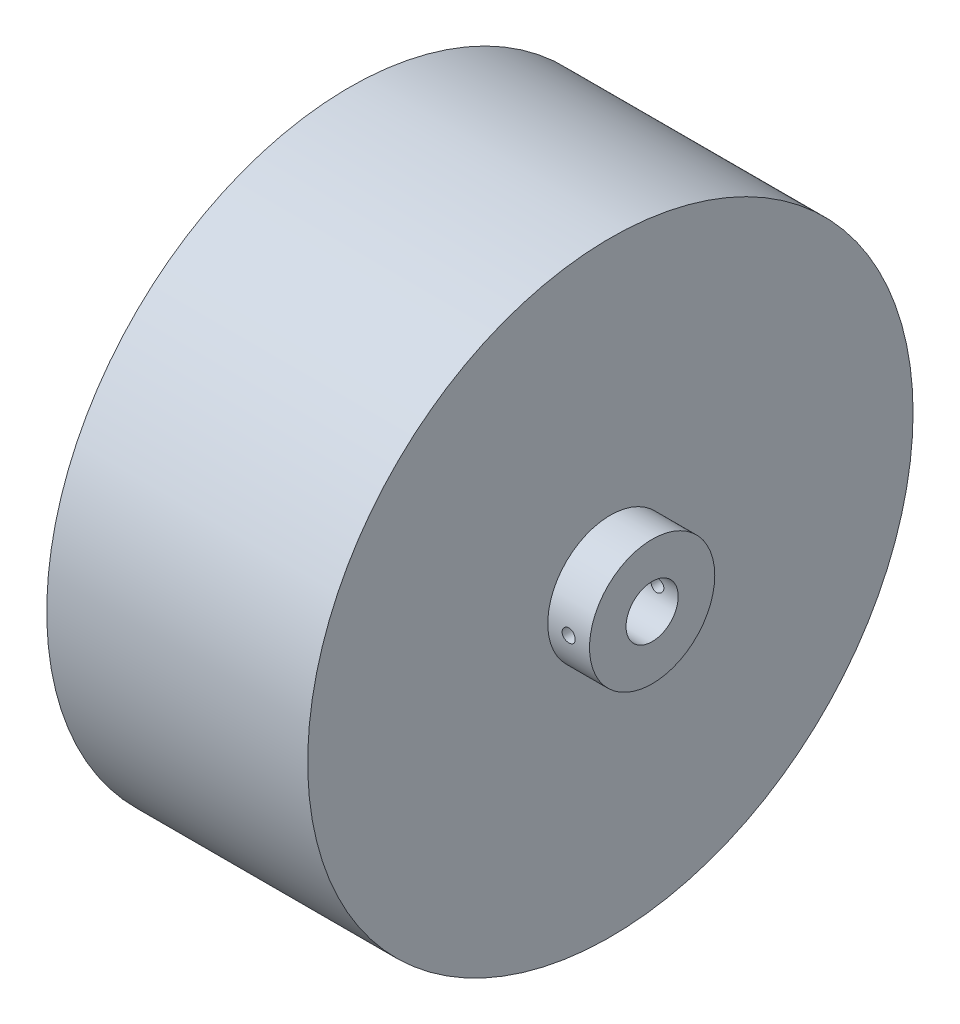
SolidWorks part; units mm, degrees
ref_plane "Front Plane" through (0, 0, 0) normal (0, 0, 1) x (1, 0, 0)
ref_plane "Top Plane" through (0, 0, 0) normal (0, 1, 0) x (1, 0, 0)
ref_plane "Right Plane" through (0, 0, 0) normal (1, 0, 0) x (0, 0, -1)
sketch "Sketch1" plane through (0, 0, 0) normal (1, 0, 0) x (0, 0, -1)
  circle A0 centre (0, 0) radius 36.83
  dimension "D1" = 73.66
extrude "Boss-Extrude1" add sketch "Sketch1" along normal blind 31.75
sketch "Sketch2" plane through (31.75, 0, 0) normal (1, 0, 0) x (0, 0, -1)
  circle A0 centre (0, 0) radius 3.175
  dimension "D1" = 6.35
sketch "Sketch3" plane through (31.75, 0, 0) normal (1, 0, 0) x (0, 0, -1)
  circle A0 centre (0, 0) radius 7.62
  dimension "D1" = 15.24
extrude "Boss-Extrude2" add sketch "Sketch3" along normal blind 5.08
extrude "Boss-Extrude3" add sketch "Sketch3<2>" against normal blind 5.08 from surface starting at face at (0, 0, -36.83)
sketch "Sketch3<2>" plane through (31.75, 0, 0) normal (1, 0, 0) x (0, 0, -1) same geometry as "Sketch3"
extrude "Cut-Extrude1" cut sketch "Sketch2" against normal through all both and the other way through all
sketch "Sketch4" plane through (0, 0, 0) normal (0, 0, 1) x (1, 0, 0)
  line L0 (31.75, -7.62) -> (31.75, 7.62) construction
  line L1 (15.875, 36.83) -> (15.875, -49.7876) construction
  line L2 (31.75, 36.83) -> (0, 36.83) construction
  circle A0 centre (34.29, 0) radius 0.7937
  circle A1 centre (-2.54, 0) radius 0.7937
  dimension "D1" = 1.5875
  dimension "D2" = 2.54
extrude "Cut-Extrude2" cut sketch "Sketch4" against normal through all both and the other way through all
sketch "Sketch5" plane through (0, 0, 0) normal (0, 1, 0) x (1, 0, 0)
  line L0 (0, 36.83) -> (0, -36.83) construction
  line L1 (0, -13.7482) -> (-11.3746, -13.7482)
  line L2 (0, -13.7482) -> (0, 13.2593)
  line L3 (0, 13.2593) -> (-11.3746, 13.2593)
  line L4 (-11.3746, -13.7482) -> (-11.3746, 13.2593)
extrude "Cut-Extrude3" cut sketch "Sketch5" against normal through all both and the other way through all
equation "\"D1@Sketch4\"=1/16"
